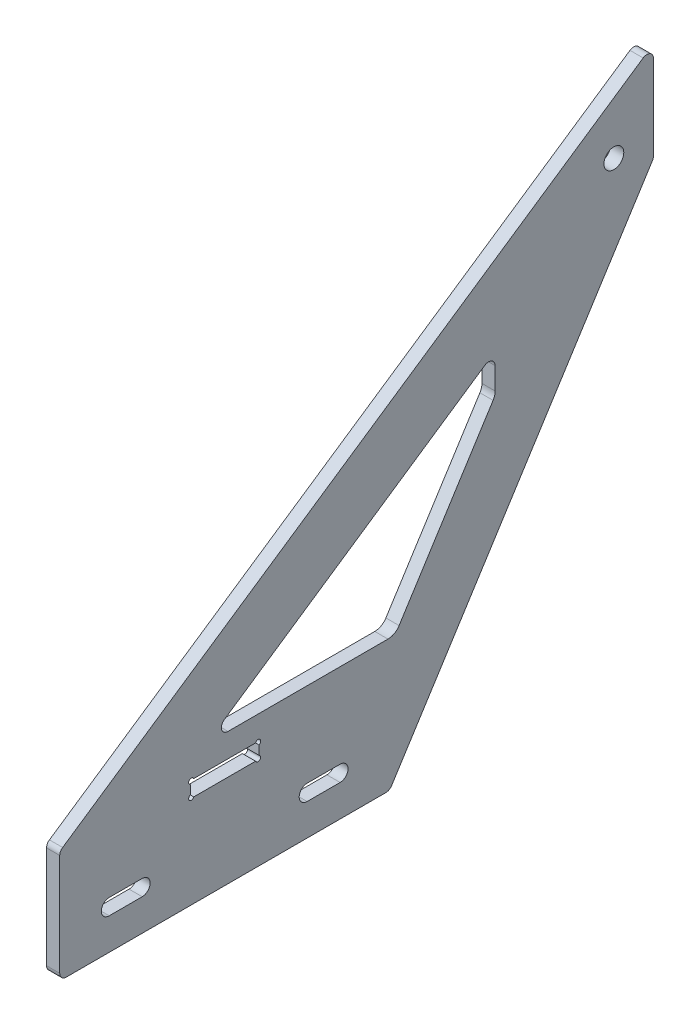
SolidWorks part; units mm, degrees
ref_plane "Front Plane" through (0, 0, 0) normal (0, 0, 1) x (1, 0, 0)
ref_plane "Top Plane" through (0, 0, 0) normal (0, 1, 0) x (1, 0, 0)
ref_plane "Right Plane" through (0, 0, 0) normal (1, 0, 0) x (0, 0, -1)
sketch "Sketch1" plane through (0, 0, 0) normal (1, 0, 0) x (0, 0, -1)
  line L0 (0, 0) -> (200, 315)
  line L1 (200, 315) -> (200, 390)
  line L2 (200, 390) -> (-250, 85)
  line L3 (-250, 85) -> (-250, 0)
  line L4 (-250, 0) -> (0, 0)
  dimension "D1" = 85
  dimension "D2" = 250
  dimension "D3" = 75
  dimension "D4" = 390
  dimension "D5" = 450
base flange "Base-Flange1" sketch "Sketch1" thickness 10 reverse thickness direction no parameters "D1"=6.2
sketch "Sketch6" plane through (0, 0, 0) normal (1, 0, 0) x (0, 0, -1)
  line L0 (-212.5, 30) -> (-187.5, 30) construction
  line L1 (-212.5, 36) -> (-187.5, 36)
  line L2 (-212.5, 24) -> (-187.5, 24)
  line L3 (-250, 0) -> (0, 0) construction
  line L4 (-125, 0) -> (-125, 85.4386) construction
  line L5 (-37.5, 30) -> (-62.5, 30) construction
  line L6 (-37.5, 36) -> (-62.5, 36)
  line L7 (-37.5, 24) -> (-62.5, 24)
  arc A0 (-212.5, 36) -> (-212.5, 24) centre (-212.5, 30) ccw
  arc A1 (-187.5, 24) -> (-187.5, 36) centre (-187.5, 30) ccw
  arc A2 (-37.5, 36) -> (-37.5, 24) centre (-37.5, 30) cw
  arc A3 (-62.5, 24) -> (-62.5, 36) centre (-62.5, 30) cw
  point P2 (-200, 30)
  point P13 (-50, 30)
  dimension "D1" = 6
  dimension "D2" = 25
  dimension "D3" = 30
  dimension "D4" = 150
extrude "Cut-Extrude1" cut sketch "Sketch6" against normal through all normal cut yes
sketch "Sketch7" plane through (0, 0, 0) normal (1, 0, 0) x (0, 0, -1)
  line L0 (80, 248.2642) -> (-138.7505, 100)
  line L1 (-138.7505, 100) -> (4.2653, 100)
  line L2 (4.2653, 100) -> (80, 219.2822)
  line L3 (80, 219.2822) -> (80, 248.2642)
  line L4 (200, 390) -> (-250, 85) construction
  line L5 (0, 0) -> (200, 315) construction
  line L6 (200, 315) -> (200, 390) construction
  line L7 (-250, 0) -> (0, 0) construction
  dimension "D1" = 50
  dimension "D2" = 50
  dimension "D3" = 120
  dimension "D4" = 100
extrude "Cut-Extrude2" cut sketch "Sketch7" against normal through all normal cut yes
fillet "Fillet1" radius 10 2 edges at (-5, 219.2822, -80) (-5, 100, -4.2653)
fillet "Fillet2" radius 5 7 edges at (-5, 390, -200) (-5, 315, -200) (-5, 0, 0) (-5, 85, 250) (-5, 0, 250) (-5, 100, 138.7505) (-5, 248.2642, -80)
sketch "Sketch8" plane through (0, 0, 0) normal (1, 0, 0) x (0, 0, -1)
  line L0 (200, 316.4532) -> (200, 380.5709) construction
  line L1 (-245, 0) -> (-2.7481, 0) construction
  circle A0 centre (170, 330) radius 7.5
  dimension "D1" = 15
  dimension "D2" = 30
  dimension "D3" = 330
extrude "Cut-Extrude3" cut sketch "Sketch8" against normal through all normal cut yes
sketch "Sketch9" plane through (0, 0, 0) normal (1, 0, 0) x (0, 0, -1)
  line L0 (-245, 0) -> (-2.7481, 0) construction
  line L1 (-151, 82) -> (-99, 82)
  line L2 (-151, 82) -> (-151, 70)
  line L3 (-151, 70) -> (-99, 70)
  line L4 (-99, 82) -> (-99, 70)
  line L5 (-250, 82.3486) -> (-250, 5) construction
  point P6 (-125, 70)
  dimension "D1" = 52
  dimension "D2" = 12
  dimension "D3" = 70
  dimension "D4" = 125
extrude "Cut-Extrude4" cut sketch "Sketch9" against normal through all normal cut yes
sketch "Sketch10" plane through (0, 0, 0) normal (1, 0, 0) x (0, 0, -1)
  line L0 (-150.2929, 70.7071) -> (-151, 70) construction
  line L1 (-151, 70) -> (-99, 70) construction
  line L2 (-151, 76) -> (-125, 76) construction
  line L3 (-151, 82) -> (-151, 70) construction
  line L4 (-125, 76) -> (-125, 82) construction
  line L5 (-99, 82) -> (-151, 82) construction
  line L6 (-150.2929, 81.2929) -> (-151, 82) construction
  line L7 (-99.7071, 81.2929) -> (-99, 82) construction
  line L8 (-99.7071, 70.7071) -> (-99, 70) construction
  circle A0 centre (-150.2929, 70.7071) radius 2
  circle A1 centre (-150.2929, 81.2929) radius 2
  circle A2 centre (-99.7071, 81.2929) radius 2
  circle A3 centre (-99.7071, 70.7071) radius 2
  dimension "D1" = 45
  dimension "D3" = 4
  dimension "D2" = 1
extrude "Cut-Extrude5" cut sketch "Sketch10" against normal through all normal cut yes
sketch "Bend-Lines1" [suppressed] plane through (0, 0, 0) normal (0, 1, 0) x (1, 0, 0)
sketch "Bounding-Box1" [suppressed] plane through (0, 0, 0) normal (0, 1, 0) x (1, 0, 0)
sheet metal parameters "Sheet-Metal1" thickness 10 parameters "D1"=6.2
flat pattern "Flat-Pattern1" [suppressed]
sketch "Bend-Lines2" plane through (0, 0, 0) normal (0, 1, 0) x (1, 0, 0)
sketch3d "Bounding-Box2" [suppressed]
  line L0 (166.038, -118.0715, 0) -> (-317.022, 225.4378, 0) construction
  line L1 (283.06, 46.4907, 0) -> (-200, 390, 0) construction
  line L2 (166.038, -118.0715, 0) -> (283.06, 46.4907, 0) construction
  line L3 (-317.022, 225.4378, 0) -> (-200, 390, 0) construction
sheet metal parameters "Sheet-Metal2" thickness 10 parameters "D1"=6.2
flat pattern "Flat-Pattern1"
sketch "Bend-Lines2" plane through (0, 0, 0) normal (0, 1, 0) x (1, 0, 0)
sketch3d "Bounding-Box2" [suppressed]
  line L0 (-166.038, -118.0715, 0) -> (317.022, 225.4378, 0) construction
  line L1 (-283.06, 46.4907, 0) -> (200, 390, 0) construction
  line L2 (-166.038, -118.0715, 0) -> (-283.06, 46.4907, 0) construction
  line L3 (317.022, 225.4378, 0) -> (200, 390, 0) construction
sheet metal parameters "Sheet-Metal3" thickness 10 parameters "D1"=6.2
flat pattern "Flat-Pattern1"
sketch "Bend-Lines2" plane through (0, 0, 0) normal (0, 1, 0) x (1, 0, 0)
sketch3d "Bounding-Box2" [suppressed]
  line L0 (-164.8174, -116.3846, 0) -> (312.8124, 223.2632, 0) construction
  line L1 (-281.4526, 47.6337, 0) -> (196.1772, 387.2815, 0) construction
  line L2 (-164.8174, -116.3846, 0) -> (-281.4526, 47.6337, 0) construction
  line L3 (312.8124, 223.2632, 0) -> (196.1772, 387.2815, 0) construction
sheet metal parameters "Sheet-Metal4" thickness 10 parameters "D1"=6.2
flat pattern "Flat-Pattern1"
sketch "Bend-Lines2" plane through (0, 0, 0) normal (0, 1, 0) x (1, 0, 0)
sketch3d "Bounding-Box2" [suppressed]
  line L0 (-170.0779, -114.4526, 0) -> (314.1227, 213.7278, 0) construction
  line L1 (-287.867, 59.3346, 0) -> (196.3336, 387.515, 0) construction
  line L2 (-170.0779, -114.4526, 0) -> (-287.867, 59.3346, 0) construction
  line L3 (314.1227, 213.7278, 0) -> (196.3336, 387.515, 0) construction
sheet metal parameters "Sheet-Metal5" thickness 10 parameters "D1"=6.2
flat pattern "Flat-Pattern1"
sketch "Bend-Lines2" plane through (0, 0, 0) normal (0, 1, 0) x (1, 0, 0)
sketch3d "Bounding-Box2" [suppressed]
  line L0 (-170.0779, -114.4526, 0) -> (314.1227, 213.7278, 0) construction
  line L1 (-287.867, 59.3346, 0) -> (196.3336, 387.515, 0) construction
  line L2 (-170.0779, -114.4526, 0) -> (-287.867, 59.3346, 0) construction
  line L3 (314.1227, 213.7278, 0) -> (196.3336, 387.515, 0) construction
sheet metal parameters "Sheet-Metal6" thickness 10 parameters "D1"=6.2
flat pattern "Flat-Pattern1"
sketch "Bend-Lines2" plane through (0, 0, 0) normal (0, 1, 0) x (1, 0, 0)
sketch3d "Bounding-Box2" [suppressed]
  line L0 (-170.0779, -114.4526, 0) -> (314.1227, 213.7278, 0) construction
  line L1 (-287.867, 59.3346, 0) -> (196.3336, 387.515, 0) construction
  line L2 (-170.0779, -114.4526, 0) -> (-287.867, 59.3346, 0) construction
  line L3 (314.1227, 213.7278, 0) -> (196.3336, 387.515, 0) construction
